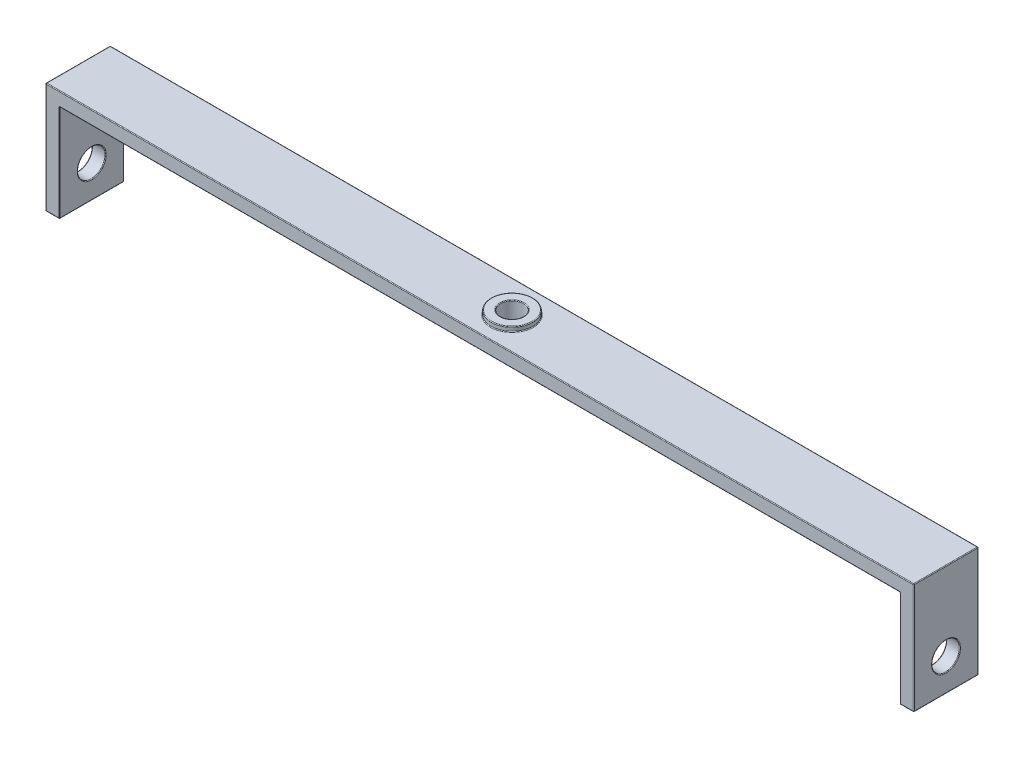
SolidWorks part; units mm, degrees
ref_plane "Front Plane" through (0, 0, 0) normal (0, 0, 1) x (1, 0, 0)
ref_plane "Top Plane" through (0, 0, 0) normal (0, 1, 0) x (1, 0, 0)
ref_plane "Right Plane" through (0, 0, 0) normal (1, 0, 0) x (0, 0, -1)
sketch "Sketch1" plane through (0, 0, 0) normal (0, 0, 1) x (1, 0, 0)
  line L0 (-47, 0) -> (47, 0)
  line L1 (-47, 0) -> (-47, -12)
  line L2 (47, 0) -> (47, -12)
  line L3 (45.5, -1.5) -> (45.5, -12)
  line L4 (-45.5, -1.5) -> (45.5, -1.5)
  line L5 (-45.5, -1.5) -> (-45.5, -12)
  line L6 (-47, -12) -> (-45.5, -12)
  line L7 (45.5, -12) -> (47, -12)
  dimension "D1" = 47
  dimension "D2" = 1.5
extrude "Boss-Extrude1" add sketch "Sketch1" along normal blind 3.5 and the other way blind 3.5
sketch "Sketch2" plane through (0, 0, 0) normal (0, 1, 0) x (1, 0, 0)
  circle A0 centre (0, 0) radius 1.25
  dimension "D1" = 2.5
extrude "Cut-Extrude1" cut sketch "Sketch2" against normal blind 3.5
sketch "Sketch3" plane through (0, 0, 0) normal (0, 1, 0) x (1, 0, 0)
  circle A1 centre (0, 0) radius 1.25
  circle A2 centre (0, 0) radius 2.25
  circle A3 centre (0, 0) radius 2.25
  dimension "D1" = 1
extrude "Boss-Extrude2" add sketch "Sketch3" along normal blind 0.5
sketch "Sketch5" plane through (-47, 0, 0) normal (-1, 0, 0) x (0, 0, 1)
  line L0 (0, 0) -> (0, -8.5) construction
  circle A0 centre (0, -8.5) radius 1.5
  dimension "D1" = 3
  dimension "D2" = 8.5
extrude "Cut-Extrude2" cut sketch "Sketch5" against normal blind 99.5
fillet "Fillet1" radius 0.075 32 edges at (-47, -8.5, 1.5) (-45.5, -8.5, -1.5) (45.5, -8.5, 1.5) (47, -8.5, -1.5) (0, 0.5, 1.25) (0, 0, 2.25) (0, 0.5, 2.25) (0, -1.5, -1.25) (-47, -6, 3.5) (-46.25, -12, 3.5) (-45.5, -6.75, 3.5) (0, -1.5, 3.5) (45.5, -6.75, 3.5) (46.25, -12, 3.5) (47, -6, 3.5) (0, 0, 3.5) (-47, -6, -3.5) (-46.25, -12, -3.5) (-45.5, -6.75, -3.5) (0, -1.5, -3.5) (45.5, -6.75, -3.5) (46.25, -12, -3.5) (47, -6, -3.5) (0, 0, -3.5) (-47, -12, 0) (-45.5, -12, 0) (-45.5, -1.5, 0) (45.5, -1.5, 0) (45.5, -12, 0) (47, -12, 0) (47, 0, 0) (-47, 0, 0)
